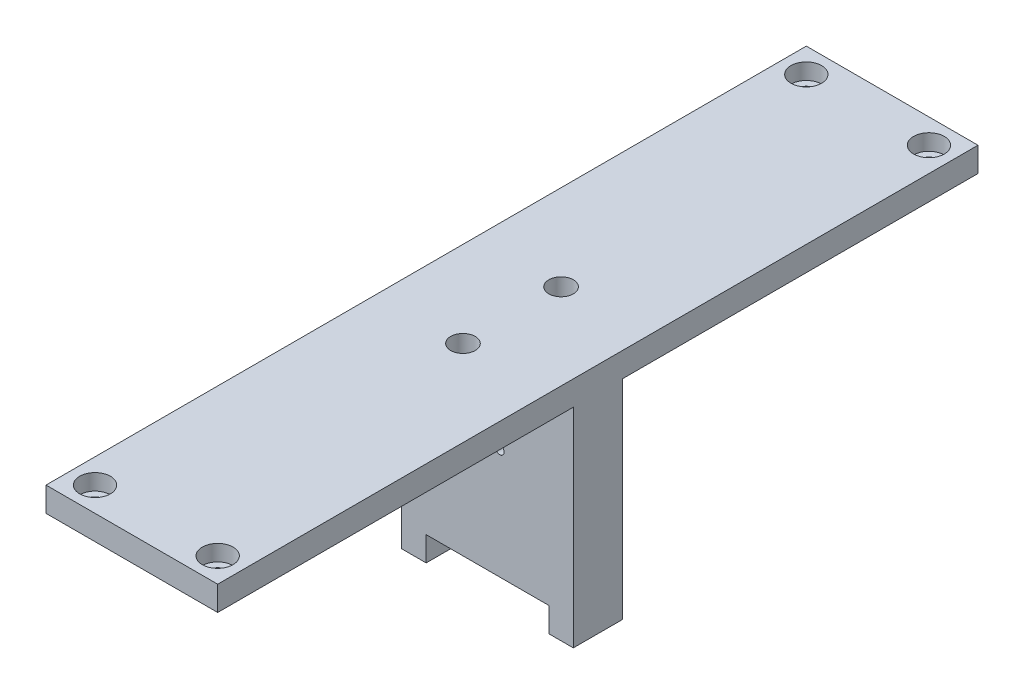
SolidWorks part; units mm, degrees
material "6061 Alloy"
ref_plane "Front Plane" through (0, 0, 0) normal (0, 0, 1) x (1, 0, 0)
ref_plane "Top Plane" through (0, 0, 0) normal (0, 1, 0) x (1, 0, 0)
ref_plane "Right Plane" through (0, 0, 0) normal (1, 0, 0) x (0, 0, -1)
sketch "Sketch1" plane through (0, 0, 0) normal (0, 1, 0) x (1, 0, 0)
  line L1 (-22.225, -98.425) -> (22.225, -98.425)
  line L2 (-22.225, -98.425) -> (-22.225, 98.425)
  line L3 (-22.225, 98.425) -> (22.225, 98.425)
  line L4 (22.225, -98.425) -> (22.225, 98.425)
  line L5 (-22.225, -98.425) -> (22.225, 98.425) construction
  line L6 (-22.225, 98.425) -> (22.225, -98.425) construction
  point P0 (0, 0)
  dimension "D1" = 196.85
  dimension "D2" = 44.45
extrude "Boss-Extrude1" add sketch "Sketch1" along normal blind 6.35
sketch "Sketch2" plane through (0, 0, 0) normal (0, -1, 0) x (-1, 0, 0)
  line L0 (-22.225, -98.425) -> (-22.225, 98.425) construction
  line L1 (22.225, 6.35) -> (-22.225, 6.35)
  line L2 (22.225, 6.35) -> (22.225, -6.35)
  line L3 (22.225, -6.35) -> (-22.225, -6.35)
  line L4 (-22.225, 6.35) -> (-22.225, -6.35)
  line L5 (22.225, 6.35) -> (-22.225, -6.35) construction
  line L6 (22.225, -6.35) -> (-22.225, 6.35) construction
  point P0 (0, 0)
  dimension "D1" = 12.7
extrude "Boss-Extrude2" add sketch "Sketch2" along normal blind 53.975
hole_wizard "CBORE for #8 Socket Head Cap Screw1" positions "Sketch4" profile "Sketch5" counterbore size "#8" standard "ANSI Inch" end condition up to next
sketch "Sketch4" plane through (0, 6.35, 0) normal (0, 1, 0) x (1, 0, 0)
  line L0 (-22.225, 98.425) -> (-22.225, -98.425) construction
  line L1 (-22.225, -98.425) -> (22.225, -98.425) construction
  line L2 (22.225, 98.425) -> (-22.225, 98.425) construction
  line L3 (22.225, -98.425) -> (22.225, 98.425) construction
  point P0 (-15.875, -92.075)
  point P2 (15.875, -92.075)
  point P4 (15.875, 92.075)
  point P6 (-15.875, 92.075)
  dimension "D1" = 6.35
  dimension "D2" = 6.35
  dimension "D3" = 6.35
  dimension "D4" = 6.35
  dimension "D5" = 6.35
  dimension "D6" = 6.35
  dimension "D7" = 6.35
  dimension "D8" = 6.35
sketch "Sketch5" plane through (-15.875, 6.35, 92.075) normal (1, 0, 0) x (0, 0, 1)
  line L0 (0, 0) -> (0, 6.35)
  line L1 (0, 6.35) -> (2.1526, 6.35)
  line L3 (2.1526, 6.35) -> (2.1527, 4.1656)
  line L4 (2.1527, 4.1656) -> (3.9687, 4.1656)
  line L5 (3.9687, 4.1656) -> (3.9687, 0)
  line L7 (3.9687, 0) -> (0, 0)
  line L11 (0, -6.35) -> (0, 107.95) construction
  dimension "Thru Hole Dia." = 4.3053
  dimension "Thru Hole Depth" = 6.35
  dimension "C'Bore Dia." = 7.9375
  dimension "C'Bore Depth" = 4.1656
sketch "Sketch6" plane through (0, -53.975, 0) normal (0, -1, 0) x (-1, 0, 0)
  line L0 (22.225, 6.35) -> (-22.225, 6.35) construction
  line L1 (15.875, 6.35) -> (-15.875, 6.35)
  line L2 (15.875, 6.35) -> (15.875, -6.35)
  line L3 (15.875, -6.35) -> (-15.875, -6.35)
  line L4 (-15.875, 6.35) -> (-15.875, -6.35)
  line L5 (-22.225, -6.35) -> (22.225, -6.35) construction
  line L6 (22.225, -6.35) -> (22.225, 6.35) construction
  line L7 (-22.225, 6.35) -> (-22.225, -6.35) construction
  dimension "D1" = 6.35
  dimension "D2" = 6.35
extrude "Cut-Extrude1" cut sketch "Sketch6" against normal blind 6.35
hole_wizard "1/4 (0.25) Diameter Hole1" positions "Sketch7" profile "Sketch8" hole size "1/4" standard "ANSI Inch" end condition through all
sketch "Sketch7" plane through (0, 6.35, 0) normal (0, 1, 0) x (1, 0, 0)
  point P0 (0, 12.7)
  point P2 (0, -12.7)
  dimension "D1" = 12.7
  dimension "D2" = 12.7
sketch "Sketch8" plane through (0, 6.35, -12.7) normal (1, 0, 0) x (0, 0, 1)
  line L0 (0, 0) -> (0, 60.325)
  line L1 (0, 60.325) -> (3.175, 60.325)
  line L2 (3.175, 60.325) -> (3.175, 0)
  line L5 (3.175, 0) -> (0, 0)
  line L11 (0, -6.35) -> (0, 107.95) construction
  dimension "Thru Hole Dia." = 6.35
  dimension "Thru Hole Depth" = 60.325
hole_wizard "#4-40 Tapped Hole1" positions "Sketch9" profile "Sketch10" tap size "#4-40" standard "ANSI Inch" end condition through all
sketch "Sketch9" plane through (0, 0, 6.35) normal (0, 0, 1) x (1, 0, 0)
  line L0 (-22.225, 6.35) -> (22.225, 6.35) construction
  point P0 (-3.175, -19.05)
  point P2 (3.175, -19.05)
  dimension "D1" = 6.35
  dimension "D2" = 3.175
  dimension "D3" = 25.4
sketch "Sketch10" plane through (-3.175, -19.05, 6.35) normal (1, 0, 0) x (0, -1, 0)
  line L0 (0, 0) -> (0, 104.775)
  line L1 (0, 104.775) -> (1.1303, 104.775)
  line L2 (1.1303, 104.775) -> (1.1303, 0)
  line L5 (1.1303, 0) -> (0, 0)
  line L11 (0, -6.35) -> (0, 107.95) construction
  dimension "Thru Tap Drill Dia." = 2.2606
  dimension "Thru Tap Drill Depth" = 104.775
cosmetic thread "Hole Thread1"
cosmetic thread "Hole Thread2"
